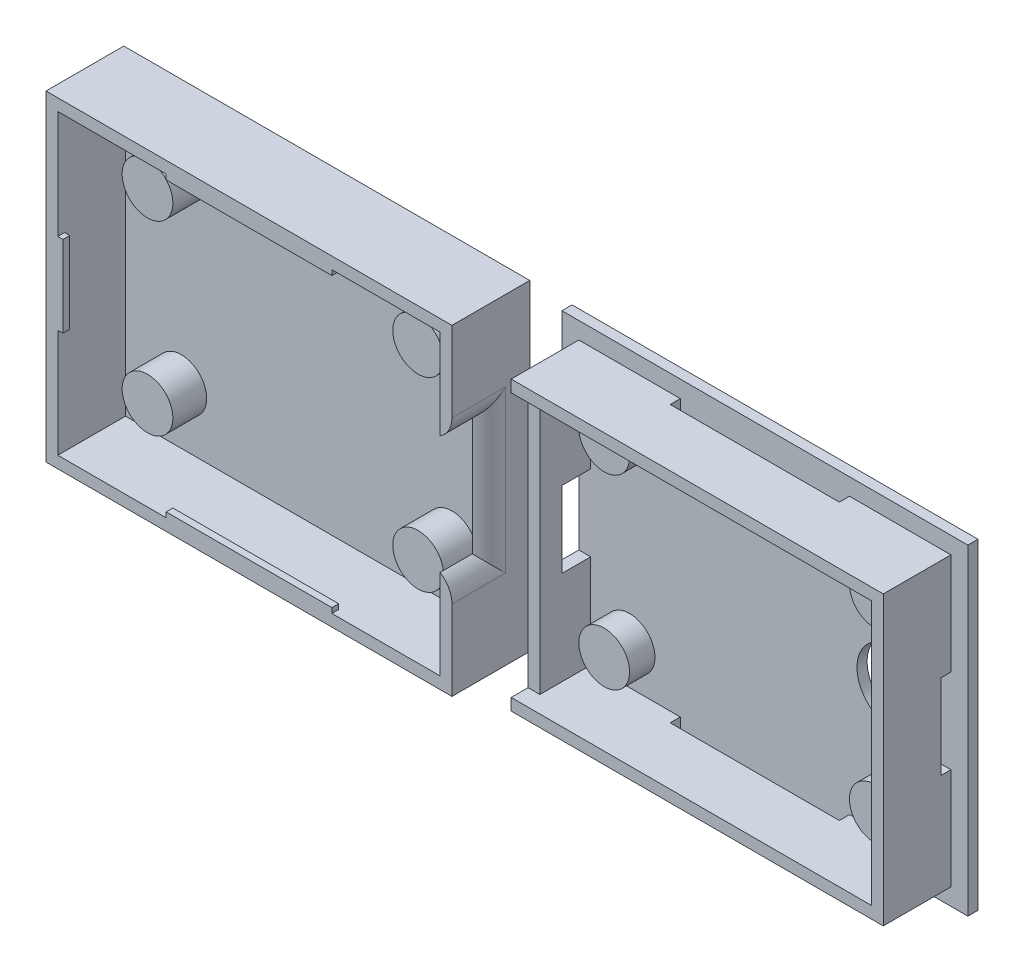
SolidWorks part; units mm, degrees
ref_plane "Alzado" through (0, 0, 0) normal (0, 0, 1) x (1, 0, 0)
ref_plane "Planta" through (0, 0, 0) normal (0, 1, 0) x (1, 0, 0)
ref_plane "Vista lateral" through (0, 0, 0) normal (1, 0, 0) x (0, 0, -1)
sketch "Croquis1" plane through (0, 0, 0) normal (0, 0, 1) x (1, 0, 0)
  line L0 (24, -19) -> (24, 19)
  line L1 (-24, 19) -> (24, 19)
  line L2 (-24, 19) -> (-24, -19)
  line L3 (-24, -19) -> (24, -19)
  line L5 (-24, 19) -> (24, -19) construction
  line L6 (-24, -19) -> (24, 19) construction
  line L7 (-20, 15) -> (20, 15) construction
  line L8 (-20, 15) -> (-20, -15) construction
  line L9 (-20, -15) -> (20, -15) construction
  line L10 (20, 15) -> (20, -15) construction
  line L11 (-20, 15) -> (20, -15) construction
  line L12 (-20, -15) -> (20, 15) construction
  line L13 (-77, 19) -> (-29, 19)
  line L14 (-77, 19) -> (-77, -19)
  line L15 (-77, -19) -> (-29, -19)
  line L16 (-29, 19) -> (-29, -19)
  line L17 (-77, 19) -> (-29, -19) construction
  line L18 (-77, -19) -> (-29, 19) construction
  circle A0 centre (15.1396, -0.0718) radius 4.25
  point P0 (0, 0)
  point P6 (0, 0)
  point P13 (-53, 0)
  dimension "D7" = 8.5
  dimension "D1" = 48
  dimension "D2" = 30
  dimension "D3" = 38
  dimension "D4" = 40
  dimension "D5" = 35.1396
  dimension "D6" = 14.9282
  dimension "D8" = 5
extrude "Saliente-Extruir1" add sketch "Croquis1" along normal blind 1.2
sketch "Croquis2" plane through (0, 0, 1.2) normal (0, 0, 1) x (1, 0, 0)
  line L0 (-26.5, 19) -> (-26.5, -19) construction
  line L1 (-29, 19) -> (-24, 19) construction
  line L4 (20.6, 15.6) -> (-20.6, 15.6)
  line L5 (-20.6, 15.6) -> (-20.6, 4.5)
  line L6 (-20.6, -15.6) -> (20.6, -15.6)
  line L7 (20.6, -15.6) -> (20.6, 15.6)
  line L8 (-22, -17) -> (22, -17)
  line L9 (22, -17) -> (22, 17)
  line L10 (22, 17) -> (-22, 17)
  line L11 (-22, 17) -> (-22, -17)
  line L12 (-22, -17) -> (22, -17)
  line L13 (22, -17) -> (22, 17)
  line L14 (22, 17) -> (-22, 17)
  line L15 (-22, 17) -> (-22, 4.5)
  line L16 (-22, 4.5) -> (-20.6, 4.5)
  line L17 (-22, -4.5) -> (-20.6, -4.5)
  line L18 (-22, -4.5) -> (-22, -17)
  line L19 (-22, 17) -> (-22, -17) construction
  line L20 (-20.6, -4.5) -> (-20.6, -15.6)
  line L21 (-20.6, 15.6) -> (-20.6, -15.6) construction
  line L22 (-20, 15) -> (20, 15) construction
  line L24 (-20, 15) -> (-20, -15) construction
  line L25 (20, 15) -> (20, -15) construction
  line L26 (-20, -15) -> (20, -15) construction
  line L31 (-29, -19) -> (-29, 19)
  line L32 (-29, 19) -> (-77, 19)
  line L33 (-77, 19) -> (-77, -19)
  line L34 (-77, -19) -> (-29, -19)
  line L35 (-29, -19) -> (-29, -7)
  line L36 (-29, 19) -> (-77, 19)
  line L37 (-77, 19) -> (-77, -19)
  line L38 (-77, -19) -> (-29, -19)
  line L41 (-30.4, 6.9982) -> (-30.4, 17.6)
  line L42 (-29, 7) -> (-29, 19)
  line L43 (-30.4, -17.6) -> (-30.4, 17.6)
  line L44 (-30.4, 17.6) -> (-75.6, 17.6)
  line L45 (-75.6, 17.6) -> (-75.6, -17.6)
  line L46 (-75.6, -17.6) -> (-30.4, -17.6)
  line L47 (-30.4, -17.6) -> (-30.4, -7.0018)
  line L48 (-30.4, 17.6) -> (-75.6, 17.6)
  line L49 (-75.6, 17.6) -> (-75.6, -17.6)
  line L50 (-75.6, -17.6) -> (-30.4, -17.6)
  line L51 (-29, 7) -> (-29, -7)
  line L52 (-30.4, 6.9982) -> (-30.4, -7.0018)
  circle A0 centre (-16, 11) radius 3
  circle A1 centre (16, 11) radius 3
  circle A2 centre (-16, -11) radius 3
  circle A3 centre (16, -11) radius 3
  circle A4 centre (-69, 11) radius 3
  circle A5 centre (-69, -11) radius 3
  circle A6 centre (-37, -11) radius 3
  circle A7 centre (-37, 11) radius 3
  dimension "D5" = 6
  dimension "D3" = 4.5
  dimension "D4" = 4.5
  dimension "D6" = 4
  dimension "D7" = 4
  dimension "D8" = 4
  dimension "D9" = 4
  dimension "D10" = 0
  dimension "D1" = 2
  dimension "D2" = 1.4
  dimension "D11" = 1.4
extrude "Saliente-Extruir2" add sketch "Croquis2" along normal blind 8 contours L51 L42 L36 L37 L38 L35 L41 L52 L47 L50 L49 L48 | A6 | A5 | A4 | A7 | A0 | A2 | A3 | A1 | L14 L15 L16 L5 L4 L7 L6 L20 L17 L18 L12 L13 region at (-53, -18.3878, 1.2) region at (-16, 11, 1.2) region at (16, 11, 1.2) region at (-16, -11, 1.2) region at (16, -11, 1.2) region at (-69, 11, 1.2) region at (-69, -11, 1.2) region at (-37, -11, 1.2) region at (-37, 11, 1.2)
sketch "Croquis3" plane through (0, -17, 0) normal (0, -1, 0) x (1, 0, 0)
  line L0 (-10, 1.2) -> (-10, 2.4)
  line L1 (-24, 1.2) -> (24, 1.2) construction
  line L2 (-10, 2.4) -> (10, 2.4)
  line L3 (10, 2.4) -> (10, 1.2)
  line L4 (-22, 1.2) -> (22, 1.2) construction
  line L5 (10, 1.2) -> (-10, 1.2)
  point P4 (0, 2.4)
  dimension "D1" = 20
  dimension "D2" = 1.2
extrude "Cortar-Extruir1" cut sketch "Croquis3" against normal up to surface (34 mm away) up to face at (0, 17, 5.2)
sketch "Croquis4" plane through (0, 0, 9.2) normal (0, 0, 1) x (1, 0, 0)
  circle A5 centre (16, -11) radius 3
  circle A6 centre (-16, -11) radius 3
  circle A7 centre (-16, 11) radius 3
  circle A8 centre (16, 11) radius 3
  circle A9 centre (16, 11) radius 3
  dimension "D1" = 0
extrude "Cortar-Extruir2" cut sketch "Croquis4" against normal blind 5
sketch "Croquis7" plane through (0, 0, 9.2) normal (0, 0, 1) x (1, 0, 0)
  line L0 (-30.4, 7) -> (-29, 7)
  line L3 (-30.4, -17.6) -> (-30.4, 17.6) construction
  line L4 (-29, 19) -> (-29, -19) construction
  line L6 (-29, 7) -> (-29, -7)
  line L7 (-29, -7) -> (-30.4, -7)
  line L8 (-30.4, -7) -> (-30.4, 7)
  point P6 (-29, 0)
  dimension "D1" = 14
extrude "Cortar-Extruir3" cut sketch "Croquis7" against normal blind 3.8
sketch "Croquis8" plane through (22, 0, 0) normal (1, 0, 0) x (0, 0, -1)
  line L0 (-1.2, 5) -> (-1.2, -5)
  line L1 (-1.2, -19) -> (-1.2, 19) construction
  line L2 (-1.2, -17) -> (-1.2, 17) construction
  line L3 (-1.2, -5) -> (-2.4, -5)
  line L4 (-2.4, -5) -> (-2.4, 5)
  line L5 (-2.4, 5) -> (-1.2, 5)
  point P6 (-1.2, 0)
  dimension "D1" = 10
  dimension "D2" = 1.2
extrude "Cortar-Extruir4" cut sketch "Croquis8" against normal up to next
sketch "Croquis9" plane through (0, 0, 9.2) normal (0, 0, 1) x (1, 0, 0)
  line L0 (-75.6, 4.8) -> (-75, 4.8)
  line L2 (-75.6, 17.6) -> (-75.6, -17.6) construction
  line L3 (-75, 4.8) -> (-75, -4.8)
  line L5 (-75, -4.8) -> (-75.6, -4.8)
  line L6 (-62.8, -17.6) -> (-62.8, -17)
  line L8 (-62.8, -17) -> (-43.2, -17)
  line L9 (-43.2, -17) -> (-43.2, -17.6)
  line L10 (-75.6, -17.6) -> (-30.4, -17.6) construction
  line L11 (-75.6, 17.6) -> (-75.6, -17.6) construction
  line L14 (-62.8, -17.6) -> (-43.2, -17.6)
  line L15 (-62.8, 17.6) -> (-62.8, 17)
  line L16 (-30.4, 17.6) -> (-75.6, 17.6) construction
  line L17 (-62.8, 17) -> (-43.2, 17)
  line L18 (-43.2, 17) -> (-43.2, 17.6)
  line L19 (-75.6, -17.6) -> (-30.4, -17.6) construction
  line L20 (-75.6, 4.8) -> (-75.6, -4.8)
  line L21 (-30.4, 17.6) -> (-75.6, 17.6) construction
  line L22 (-43.2, 17.6) -> (-62.8, 17.6)
  line L23 (-29, 19) -> (-77, 19) construction
  point P4 (-75, 0)
  point P14 (-53, -17.6)
  point P19 (-53, -17)
  point P24 (-53, 17)
  point P30 (-53, 19)
  dimension "D1" = 0.6
  dimension "D2" = 9.6
  dimension "D3" = 0.6
  dimension "D4" = 19.6
  dimension "D5" = 0.6
  dimension "D6" = 19.6
extrude "Saliente-Extruir3" add sketch "Croquis9" against normal blind 0.8
sketch "Croquis11" plane through (0, 0, 9.2) normal (0, 0, 1) x (1, 0, 0)
  circle A0 centre (-37, -11) radius 3 construction
  circle A1 centre (-37, 11) radius 3 construction
  circle A2 centre (-69, 11) radius 3 construction
  circle A3 centre (-69, -11) radius 3 construction
  circle A4 centre (-37, -11) radius 3
  circle A5 centre (-37, 11) radius 3
  circle A6 centre (-69, 11) radius 3
  circle A7 centre (-69, -11) radius 3
extrude "Cortar-Extruir5" cut sketch "Croquis11" against normal blind 4
sketch "Croquis12" plane through (0, 0, 1.2) normal (0, 0, 1) x (1, 0, 0)
  line L0 (-22, -7) -> (-22, 7)
  line L1 (-22, -4.5) -> (-22, -17) construction
  line L2 (-22, 17) -> (-22, 4.5) construction
  line L3 (-22, -7) -> (-24, -7)
  line L4 (-24, 19) -> (-24, -19) construction
  line L5 (-24, -7) -> (-24, 7)
  line L6 (-24, 7) -> (-22, 7)
  point P6 (-22, 0)
  dimension "D1" = 14
extrude "Cortar-Extruir6" cut sketch "Croquis12" against normal up to next
fillet "Redondeo1" radius 3 2 edges at (-29, -7, 7.3) (-29, 7, 7.3)
fillet "Redondeo2" radius 3 2 edges at (-24, -7, 0.6) (-24, 7, 0.6)
sketch "Croquis13" plane through (0, 0, 9.2) normal (0, 0, 1) x (1, 0, 0)
  line L0 (-22, 4.5) -> (-22, -4.5)
  line L1 (-22, -4.5) -> (-20.6, -4.5)
  line L2 (-20.6, -4.5) -> (-20.6, 4.5)
  line L3 (-20.6, 4.5) -> (-22, 4.5)
extrude "Saliente-Extruir4" add sketch "Croquis13" against normal blind 4.6
fillet "Redondeo3" radius 3 1 edges at (-29, 0, 5.4)
sketch "Croquis14" plane through (0, 0, 9.2) normal (0, 0, 1) x (1, 0, 0)
  line L0 (-20.6, -15.6) -> (-22, -15.6)
  line L1 (-22, -7) -> (-22, -17) construction
  line L2 (-22, -15.6) -> (-22, 15.6)
  line L3 (-22, 17) -> (-22, -17) construction
  line L4 (-22, 15.6) -> (-20.6, 15.6)
  line L5 (-20.6, 15.6) -> (-20.6, -15.6)
extrude "Cortar-Extruir7" cut sketch "Croquis14" against normal blind 2
